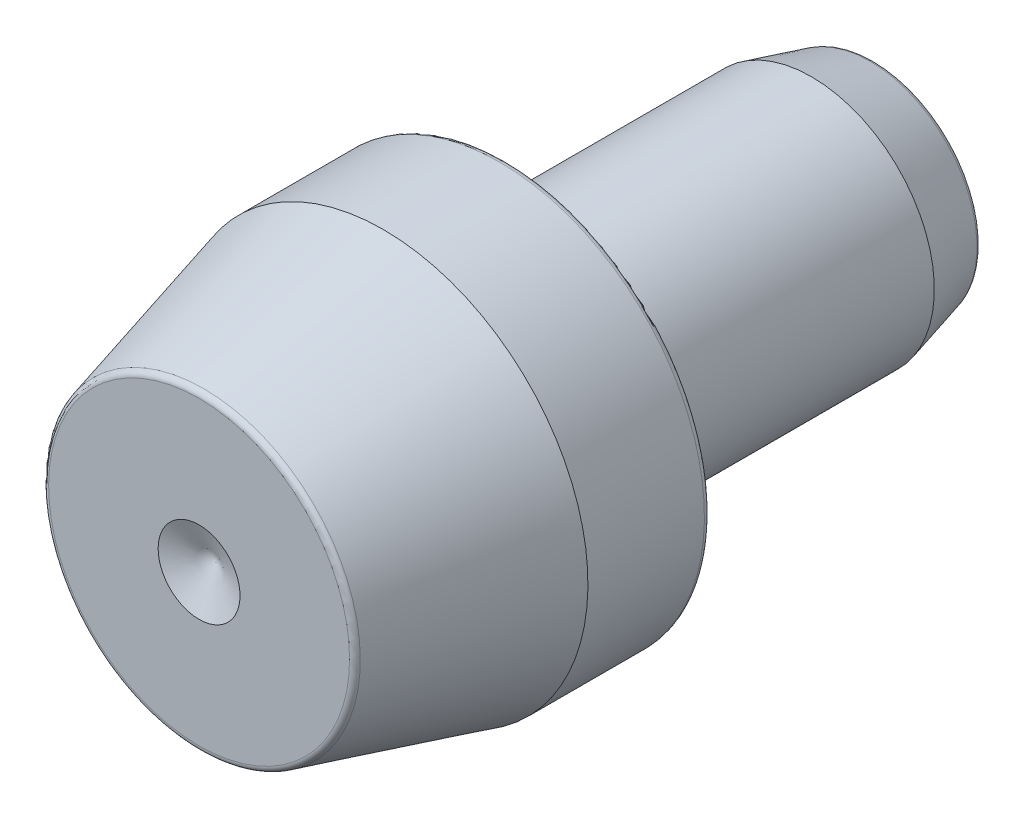
SolidWorks part; units mm, degrees
ref_plane "Front Plane" through (0, 0, 0) normal (0, 0, 1) x (1, 0, 0)
ref_plane "Top Plane" through (0, 0, 0) normal (0, 1, 0) x (1, 0, 0)
ref_plane "Right Plane" through (0, 0, 0) normal (1, 0, 0) x (0, 0, -1)
sketch "Sketch1" plane through (0, 0, 0) normal (1, 0, 0) x (0, 0, -1)
  line L0 (-16.5, 0) -> (16.5, 0) construction
  line L1 (-16.5, 2) -> (-16.5, 7.3525)
  line L2 (-16.2721, 7.6495) -> (-7.5, 10)
  line L3 (-7.5, 10) -> (-1.8075, 10)
  line L4 (-1.5, 9.6925) -> (-1.5, 6.9225)
  line L5 (0.345, 6) -> (13.425, 6)
  line L6 (13.425, 6) -> (16.2721, 5.2371)
  line L7 (16.5, 4.9401) -> (16.5, 0)
  line L8 (16.5, 0) -> (-15.6716, 0)
  line L9 (-16.5, 2) -> (-15.6716, 0)
  line L10 (-16.5, 2) -> (-16.5, 0) construction
  line L12 (-1.8075, 6.615) -> (-1.8075, 6)
  line L13 (-1.5, 5.6925) -> (0.0375, 5.6925)
  line L14 (0.0375, 5.6925) -> (0.345, 6)
  arc A0 (-1.5, 6.9225) -> (-1.8075, 6.615) centre (-1.5, 6.615) ccw
  arc A1 (-1.8075, 6) -> (-1.5, 5.6925) centre (-1.5, 6) ccw
  arc A2 (-1.5, 9.6925) -> (-1.8075, 10) centre (-1.8075, 9.6925) ccw
  arc A3 (-16.5, 7.3525) -> (-16.2721, 7.6495) centre (-16.1925, 7.3525) cw
  arc A4 (16.5, 4.9401) -> (16.2721, 5.2371) centre (16.1925, 4.9401) ccw
  point P20 (-16.5, 7.5885)
  point P25 (16.5, 5.1761)
  dimension "D5" = 15
  dimension "D6" = 15
  dimension "D1" = 22.5
  dimension "D2" = 2
  dimension "D3" = 45
  dimension "D7" = 0.3075
  dimension "D8" = 0.3075
  dimension "D9" = 0.9225
  dimension "D10" = 1.5375
revolve "Revolve1" add sketch "Sketch1" angle 360 about L8
ref_plane "Contact Plane 1" through (0, 0, 16.5) normal (0, 0, 1) x (1, 0, 0)
ref_axis "Center Axis 1" through (0, 0, -7.15) along (0, 0, 1)
equation "\"D4@Sketch1\"=\"C@Sketch1\"*.25625"
equation "\"D2@Sketch1\"=\"A@Sketch1\"*.1"
equation "\"D7@Sketch1\"=\"D4@Sketch1\"*.1"
equation "\"D8@Sketch1\"=\"D7@Sketch1\""
equation "\"D9@Sketch1\"=\"D7@Sketch1\"*3"
equation "\"D10@Sketch1\"=\"D4@Sketch1\"*.5"
